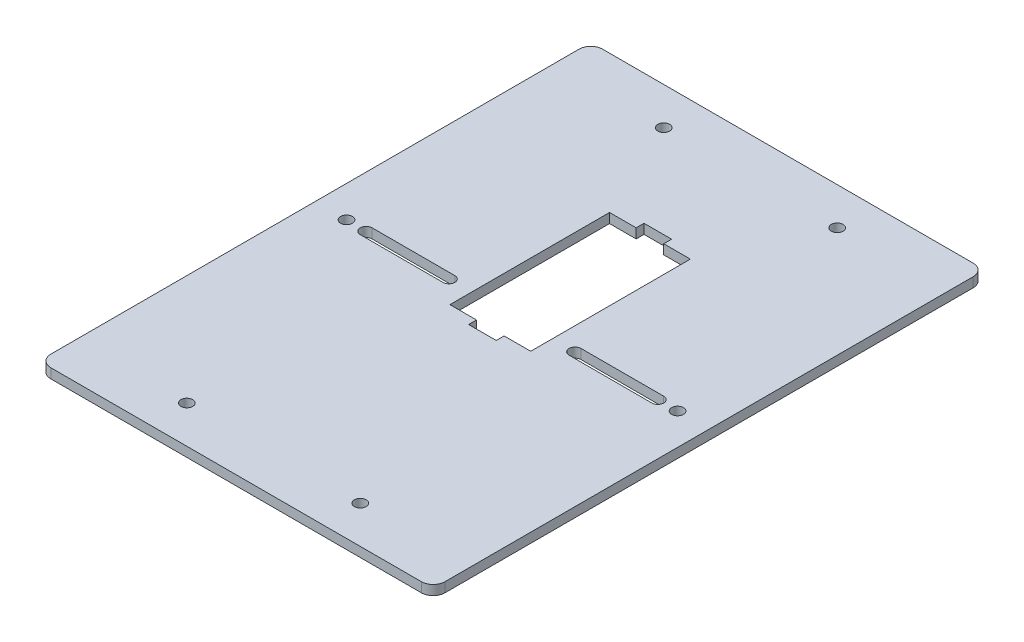
SolidWorks part; units mm, degrees
material "6061-T4 (SS)"
ref_plane "Front Plane" through (0, 0, 0) normal (0, 0, 1) x (1, 0, 0)
ref_plane "Top Plane" through (0, 0, 0) normal (0, 1, 0) x (1, 0, 0)
ref_plane "Right Plane" through (0, 0, 0) normal (1, 0, 0) x (0, 0, -1)
sketch "Sketch2" plane through (0, 0, 0) normal (0, 1, 0) x (1, 0, 0)
  line L1 (-47, -70) -> (47, -70)
  line L2 (-50, -67) -> (-50, 67)
  line L3 (-47, 70) -> (47, 70)
  line L4 (50, -67) -> (50, 67)
  line L5 (-50, -70) -> (50, 70) construction
  line L6 (-50, 70) -> (50, -70) construction
  arc A12 (47, -70) -> (50, -67) centre (47, -67) ccw
  arc A13 (47, 70) -> (50, 67) centre (47, 67) cw
  arc A14 (-50, 67) -> (-47, 70) centre (-47, 67) cw
  arc A15 (-47, -70) -> (-50, -67) centre (-47, -67) cw
  point P0 (0, 0)
  point P6 (0, 0)
  dimension "D9" = 3
  dimension "D1" = 140
  dimension "D2" = 100
base flange "Base-Flange2" sketch "Sketch2" thickness 2.45 reverse thickness direction no parameters "D1"=2
sketch "Sketch10" plane through (0, 0, 0) normal (0, 1, 0) x (1, 0, 0)
  line L0 (47, 70) -> (-47, 70) construction
  line L1 (-10.25, -5.5) -> (-3.5, -5.5)
  line L2 (-10.25, -5.5) -> (-10.25, 35)
  line L3 (-10.25, 35) -> (-3.5, 35)
  line L4 (10.25, -5.5) -> (10.25, 35)
  line L5 (-10.25, -5.5) -> (10.25, 35) construction
  line L6 (-10.25, 35) -> (10.25, -5.5) construction
  line L7 (-3.5, 35) -> (-3.5, 37)
  line L8 (-3.5, 37) -> (3.5, 37)
  line L9 (3.5, 37) -> (3.5, 35)
  line L10 (-10.25, 14.75) -> (10.25, 14.75) construction
  line L11 (3.5, -7.5) -> (3.5, -5.5)
  line L12 (-3.5, -5.5) -> (-3.5, -7.5)
  line L13 (-3.5, -7.5) -> (3.5, -7.5)
  line L14 (3.5, 35) -> (10.25, 35)
  line L15 (3.5, -5.5) -> (10.25, -5.5)
  line L16 (50, -67) -> (50, 67) construction
  line L17 (-50, 67) -> (-50, -67) construction
  line L18 (0, -1.3475) -> (0, 1.3475) construction
  line L19 (-1.3475, 0) -> (1.3475, 0) construction
  line L21 (-37, 0) -> (-16, 0) construction
  line L22 (-37, 1.5) -> (-16, 1.5)
  line L23 (-37, -1.5) -> (-16, -1.5)
  line L24 (37, 0) -> (16, 0) construction
  line L25 (37, 1.5) -> (16, 1.5)
  line L26 (37, -1.5) -> (16, -1.5)
  circle A0 centre (42, 0) radius 1.5
  circle A1 centre (-42, 0) radius 1.5
  circle A2 centre (22, 60.5) radius 1.5
  circle A3 centre (-22, 60.5) radius 1.5
  circle A4 centre (22, -60.5) radius 1.5
  circle A5 centre (-22, -60.5) radius 1.5
  arc A6 (-37, 1.5) -> (-37, -1.5) centre (-37, 0) ccw
  arc A7 (-16, -1.5) -> (-16, 1.5) centre (-16, 0) ccw
  arc A8 (37, 1.5) -> (37, -1.5) centre (37, 0) cw
  arc A9 (16, -1.5) -> (16, 1.5) centre (16, 0) cw
  point P0 (0, 14.75)
  point P11 (0, 37)
  point P39 (-26.5, 0)
  point P46 (-38.5, 0)
  point P47 (-14.5, 0)
  point P50 (26.5, 0)
  dimension "D8" = 3
  dimension "D10" = 9.5
  dimension "D11" = 3
  dimension "D1" = 20.5
  dimension "D2" = 40.5
  dimension "D3" = 35
  dimension "D4" = 2
  dimension "D5" = 7
  dimension "D6" = 8
  dimension "D7" = 8
  dimension "D9" = 28
  dimension "D12" = 24
  dimension "D13" = 3.5
extrude "Cut-Extrude1" cut sketch "Sketch10" against normal blind 2.45 normal cut yes
sketch "Bend-Lines1" [suppressed] plane through (0, 0, 0) normal (0, 1, 0) x (1, 0, 0)
sketch "Bounding-Box1" [suppressed] plane through (0, 0, 0) normal (0, 1, 0) x (1, 0, 0)
sheet metal parameters "Sheet-Metal3" thickness 2.45 parameters "D1"=2
flat pattern "Flat-Pattern3" [suppressed]
sketch "Bend-Lines3" plane through (0, 0, 0) normal (0, 1, 0) x (1, 0, 0)
sketch3d "Bounding-Box3" [suppressed]
  line L0 (-3, 137, 0) -> (-3, -3, 0) construction
  line L1 (97, 137, 0) -> (97, -3, 0) construction
  line L2 (-3, 137, 0) -> (97, 137, 0) construction
  line L3 (-3, -3, 0) -> (97, -3, 0) construction
sheet metal parameters "Sheet-Metal4" thickness 2.45 parameters "D1"=2
flat pattern "Flat-Pattern3"
sketch "Bend-Lines3" plane through (0, 0, 0) normal (0, 1, 0) x (1, 0, 0)
sketch3d "Bounding-Box3" [suppressed]
  line L0 (3, 137, 0) -> (3, -3, 0) construction
  line L1 (-97, 137, 0) -> (-97, -3, 0) construction
  line L2 (3, 137, 0) -> (-97, 137, 0) construction
  line L3 (3, -3, 0) -> (-97, -3, 0) construction
